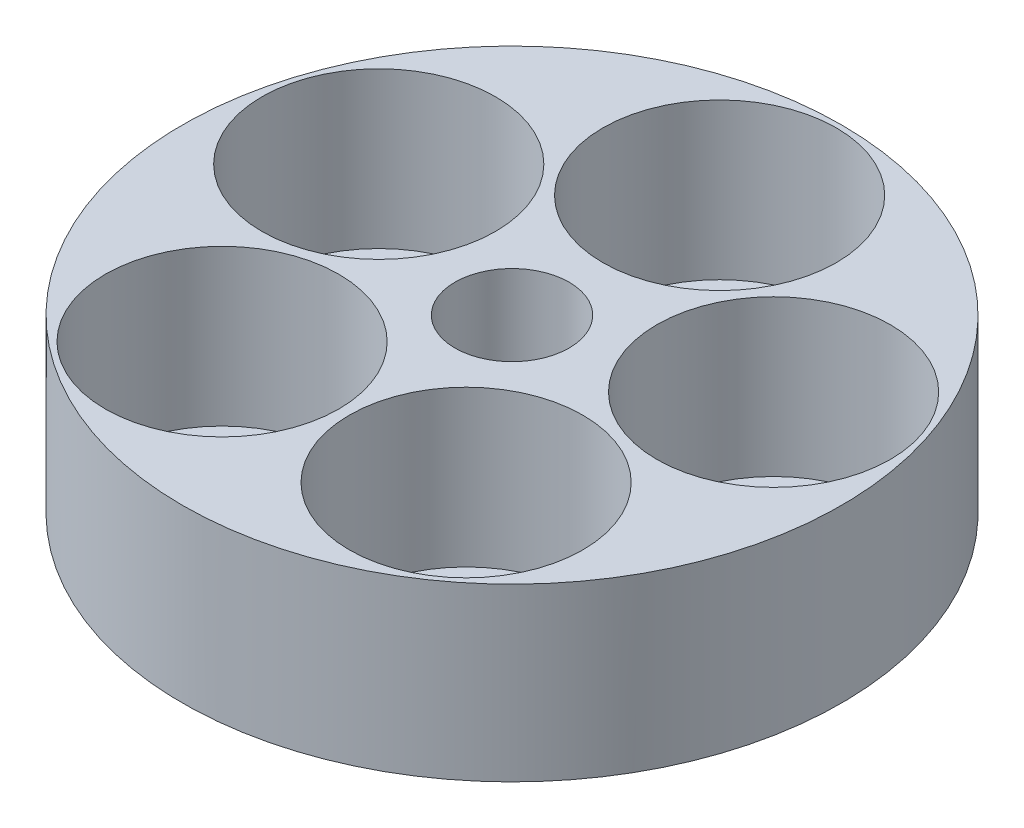
SolidWorks part; units mm, degrees
ref_plane "Front Plane" through (0, 0, 0) normal (0, 0, 1) x (1, 0, 0)
ref_plane "Top Plane" through (0, 0, 0) normal (0, 1, 0) x (1, 0, 0)
ref_plane "Right Plane" through (0, 0, 0) normal (1, 0, 0) x (0, 0, -1)
sketch "Sketch1" plane through (0, 0, 0) normal (0, 1, 0) x (1, 0, 0)
  line L0 (0, -164.5173) -> (0, 163.7587) construction
  line L1 (-104.9541, 34.1017) -> (106.3821, -34.5656) construction
  line L2 (-169.6132, -123.2312) -> (93.1873, 67.7046) construction
  line L3 (-107.5036, 0) -> (118.5963, 0) construction
  line L4 (-102.8693, -33.4243) -> (102.8693, 33.4243) construction
  line L5 (-62.7697, -86.3951) -> (62.7697, 86.3951) construction
  circle A0 centre (0, 0) radius 63.5
  circle A1 centre (38.0423, 12.3607) radius 22.5
  circle A4 centre (0, 40) radius 22.5
  circle A5 centre (-38.0423, 12.3607) radius 22.5
  circle A6 centre (-23.5114, -32.3607) radius 22.5
  circle A10 centre (23.5114, -32.3607) radius 22.5
  circle A11 centre (0, 0) radius 11
  dimension "D1" = 127
  dimension "D4" = 45
  dimension "D5" = 40
  dimension "D7" = 40
  dimension "D8" = 40
  dimension "D9" = 40
  dimension "D10" = 72
  dimension "D12" = 40
  dimension "D14" = 22
  dimension "D2" = 72
  dimension "D3" = 72
  dimension "D6" = 72
  dimension "D13" = 40
extrude "Boss-Extrude1" add sketch "Sketch1" along normal blind 30
sketch "Sketch2" plane through (0, 30, 0) normal (0, 1, 0) x (1, 0, 0)
  circle A0 centre (0, 0) radius 32.5
  circle A1 centre (0, 0) radius 50
  dimension "D1" = 65
  dimension "D2" = 100
sketch "Sketch3" plane through (0, 30, 0) normal (0, 1, 0) x (1, 0, 0)
  line L0 (-63.5, 0) -> (63.5, 0)
  line L1 (0, 63.5) -> (0, -63.5)
  circle A0 centre (0, 0) radius 63.5 construction
sketch "Sketch4" plane through (0, 0, 0) normal (0, -1, 0) x (1, 0, 0)
  circle A0 centre (0, 0) radius 63.5
  circle A1 centre (0, 0) radius 11
extrude "Boss-Extrude2" add sketch "Sketch4" along normal blind 3
